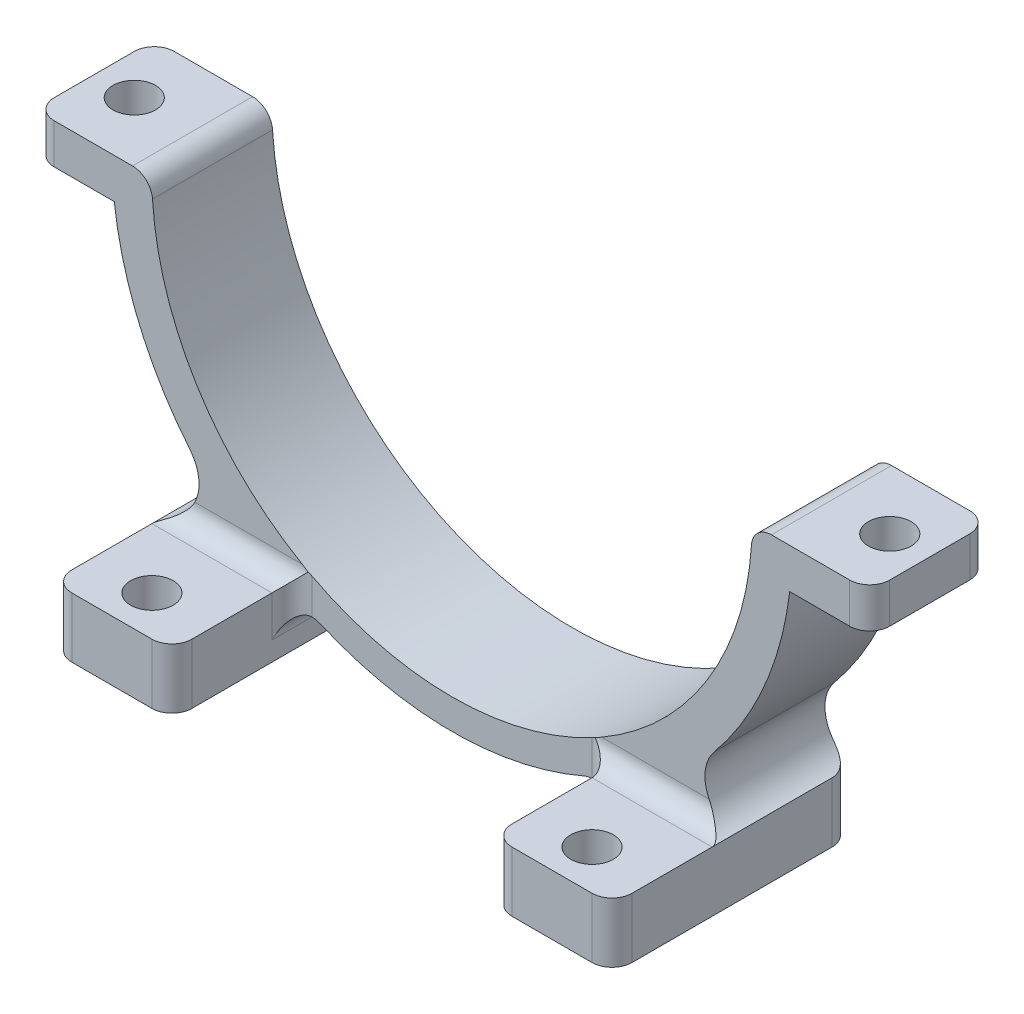
SolidWorks part; units mm, degrees
ref_plane "Front Plane" through (0, 0, 0) normal (0, 0, 1) x (1, 0, 0)
ref_plane "Top Plane" through (0, 0, 0) normal (0, 1, 0) x (1, 0, 0)
ref_plane "Right Plane" through (0, 0, 0) normal (1, 0, 0) x (0, 0, -1)
sketch "Sketch1" plane through (0, 0, 0) normal (0, 0, 1) x (1, 0, 0)
  line L0 (0, 0) -> (0, 50000) construction
  line L1 (-47.625, 0) -> (-66.3002, 0)
  line L2 (-66.3002, 0) -> (-66.3002, -6.35)
  line L3 (-66.3002, -6.35) -> (-53.6002, -6.35)
  line L4 (44.45, -53.975) -> (-44.45, -53.975)
  line L5 (-44.45, -53.975) -> (-44.45, -44.45)
  line L6 (-44.45, -44.45) -> (-30.6186, -44.45)
  line L7 (47.625, 0) -> (66.3002, 0)
  line L8 (66.3002, 0) -> (66.3002, -6.35)
  line L9 (66.3002, -6.35) -> (53.6002, -6.35)
  line L10 (44.45, -44.45) -> (30.6186, -44.45)
  line L11 (44.45, -53.975) -> (44.45, -44.45)
  circle A1 centre (0, 0) radius 44.45 construction
  arc A2 (-47.625, 0) -> (47.625, 0) centre (0, 0) ccw
  arc A3 (-53.6002, -6.35) -> (-30.6186, -44.45) centre (0, 0) ccw
  arc A4 (53.6002, -6.35) -> (30.6186, -44.45) centre (0, 0) cw
  point P7 (0, -47.625)
  point P11 (0, 0)
  point P13 (-28.1913, -45.1004)
  point P16 (-34.925, -53.975)
  point P23 (0, -53.975)
  dimension "D1" = 3.175
  dimension "D2" = 88.9
  dimension "D3" = 6.35
  dimension "D4" = 6.35
  dimension "D5" = 9.525
  dimension "D6" = 12.7
  dimension "D7" = 34.925
  dimension "D8" = 9.525
  dimension "D9" = 6.35
extrude "Boss-Extrude2" add sketch "Sketch1" along normal mid plane 19.05
sketch "Sketch5" plane through (0, -6.35, 0) normal (0, -1, 0) x (1, 0, 0)
  line L0 (0, 0) -> (0, 50000) construction
  line L1 (-66.3002, 9.525) -> (-53.6002, 9.525) construction
  line L2 (-66.3002, 9.525) -> (-66.3002, -9.525) construction
  circle A0 centre (-59.9502, 0) radius 3.3782
  circle A1 centre (59.9502, 0) radius 3.3782
  point P7 (-59.9502, 9.525)
  point P10 (-66.3002, 0)
  dimension "D1" = 6.7564
extrude "Cut-Extrude2" cut sketch "Sketch5" against normal up to next
sketch "Sketch6" plane through (0, 0, 9.525) normal (0, 0, 1) x (1, 0, 0)
  line L0 (-44.45, -53.975) -> (44.45, -53.975) construction
  line L1 (-44.45, -44.45) -> (-25.4, -44.45)
  line L2 (-44.45, -44.45) -> (-44.45, -53.975)
  line L3 (-44.45, -53.975) -> (-25.4, -53.975)
  line L4 (-25.4, -44.45) -> (-25.4, -53.975)
  line L5 (0, 0) -> (0, 50000) construction
  line L6 (44.45, -53.975) -> (25.4, -53.975)
  line L7 (25.4, -44.45) -> (25.4, -53.975)
  line L8 (44.45, -44.45) -> (25.4, -44.45)
  line L9 (44.45, -44.45) -> (44.45, -53.975)
  dimension "D1" = 19.05
extrude "Boss-Extrude3" add sketch "Sketch6" along normal blind 19.05
sketch "Sketch7" plane through (0, -44.45, 0) normal (0, 1, 0) x (1, 0, 0)
  line L1 (-25.4, -28.575) -> (-44.45, -28.575) construction
  line L3 (0, 0) -> (0, 50000) construction
  circle A0 centre (-34.925, -22.225) radius 3.3782
  circle A1 centre (34.925, -22.225) radius 3.3782
  point P5 (-34.925, -28.575)
  dimension "D2" = 6.7564
  dimension "D1" = 6.35
extrude "Cut-Extrude3" cut sketch "Sketch7" against normal up to next
sketch "Sketch10" plane through (0, 0, 9.525) normal (0, 0, 1) x (1, 0, 0)
  line L0 (-25.4, -53.975) -> (-25.4, -44.45) construction
  line L1 (25.4, -44.45) -> (25.4, -53.975) construction
  line L2 (-25.4, -45.818) -> (-25.4, -53.975)
  line L3 (-25.4, -53.975) -> (25.4, -53.975)
  line L4 (25.4, -53.975) -> (25.4, -45.818)
  arc A0 (-25.4, -45.818) -> (25.4, -45.818) centre (0, 0) ccw
  arc A1 (-47.625, 0) -> (47.625, 0) centre (0, 0) ccw construction
  dimension "D1" = 4.7625
extrude "Cut-Extrude5" cut sketch "Sketch10" against normal up to next
fillet "Fillet3" radius 6.35 2 edges at (30.6186, -44.45, 0) (-30.6186, -44.45, 0)
fillet "Fillet4" radius 3.175 18 edges at (47.625, 0, 0) (-47.625, 0, 0) (25.4, -45.818, 0) (25.4, -45.134, 9.525) (34.925, -44.45, 9.525) (-25.4, -45.818, 0) (-25.4, -45.134, 9.525) (-34.925, -44.45, 9.525) (-66.3002, -3.175, 9.525) (-66.3002, -3.175, -9.525) (66.3002, -3.175, -9.525) (66.3002, -3.175, 9.525) (25.4, -49.2125, 28.575) (44.45, -49.2125, 28.575) (-44.45, -49.2125, 28.575) (-25.4, -49.2125, 28.575) (44.45, -49.2125, -9.525) (-44.45, -49.2125, -9.525)
